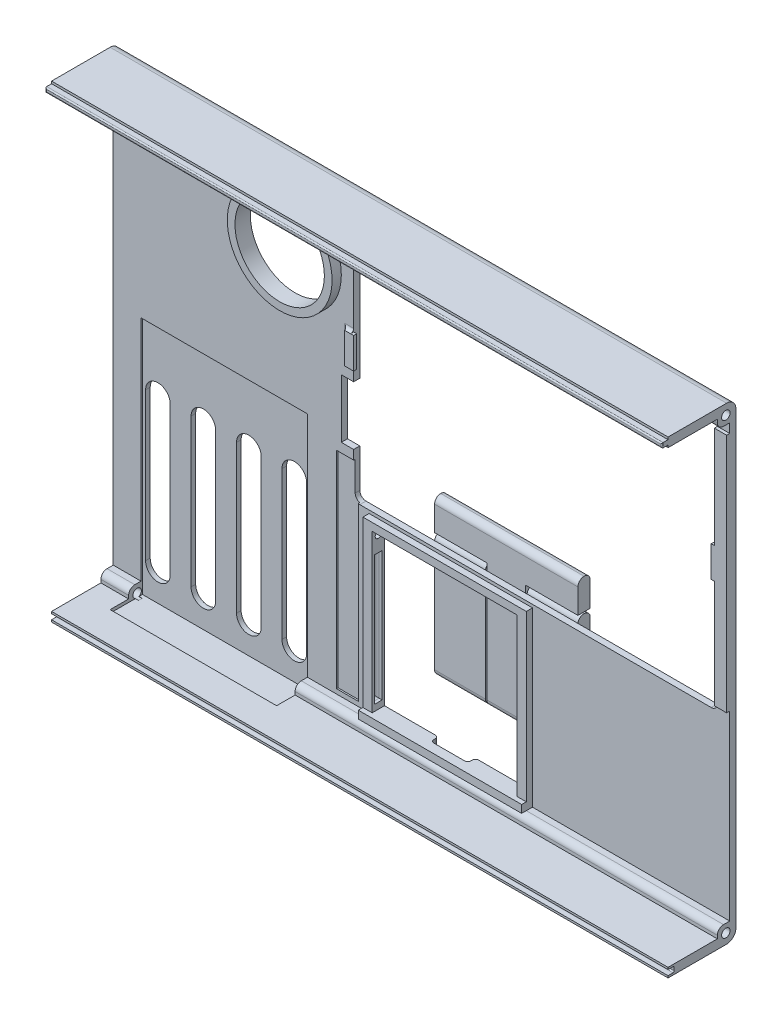
SolidWorks part; units mm, degrees
ref_plane "Front Plane" through (0, 0, 0) normal (0, 0, 1) x (1, 0, 0)
ref_plane "Top Plane" through (0, 0, 0) normal (0, 1, 0) x (1, 0, 0)
ref_plane "Right Plane" through (0, 0, 0) normal (1, 0, 0) x (0, 0, -1)
sketch "Sketch1" plane through (0, 0, 0) normal (0, 0, 1) x (1, 0, 0)
  line L1 (105, -90.3987) -> (-95, -90.3987)
  line L2 (105, -90.3987) -> (105, 61.6013)
  line L3 (105, 61.6013) -> (-95, 61.6013)
  line L4 (-95, -90.3987) -> (-95, 61.6013)
  line L5 (105, -90.3987) -> (-95, 61.6013) construction
  line L6 (105, 61.6013) -> (-95, -90.3987) construction
  point P0 (5, -14.3987)
  dimension "D1" = 200
  dimension "D2" = 152
extrude "body" add sketch "Sketch1" along normal blind 2
sketch "Sketch3" plane through (0, 0, 0) normal (0, 0, -1) x (-1, 0, 0)
  line L0 (95, -54.3987) -> (-105, -54.3987) construction
  line L1 (95, 61.6013) -> (95, -90.3987) construction
  line L2 (-105, -90.3987) -> (-105, 61.6013) construction
  line L3 (66.25, -78.3987) -> (66.25, -30.3987) construction
  line L4 (62.25, -78.3987) -> (62.25, -30.3987)
  line L5 (70.25, -78.3987) -> (70.25, -30.3987)
  line L6 (95, -30.3987) -> (-105, -30.3987) construction
  line L7 (81, -78.3987) -> (81, -30.3987) construction
  line L8 (95, -78.3987) -> (-105, -78.3987) construction
  line L9 (77, -78.3987) -> (77, -30.3987)
  line L10 (85, -78.3987) -> (85, -30.3987)
  line L11 (51.5, -78.3987) -> (51.5, -30.3987) construction
  line L12 (47.5, -78.3987) -> (47.5, -30.3987)
  line L13 (55.5, -78.3987) -> (55.5, -30.3987)
  line L14 (36.75, -78.3987) -> (36.75, -30.3987) construction
  line L15 (32.75, -78.3987) -> (32.75, -30.3987)
  line L16 (40.75, -78.3987) -> (40.75, -30.3987)
  line L17 (95, -90.3987) -> (95, 61.6013) construction
  line L18 (-105, 61.6013) -> (95, 61.6013) construction
  line L19 (95, -90.3987) -> (-105, -90.3987) construction
  line L20 (-105, -90.3987) -> (-105, 61.6013) construction
  circle A0 centre (38, 34.1013) radius 14.5
  arc A1 (62.25, -78.3987) -> (70.25, -78.3987) centre (66.25, -78.3987) ccw
  arc A2 (70.25, -30.3987) -> (62.25, -30.3987) centre (66.25, -30.3987) ccw
  arc A3 (77, -78.3987) -> (85, -78.3987) centre (81, -78.3987) ccw
  arc A4 (85, -30.3987) -> (77, -30.3987) centre (81, -30.3987) ccw
  arc A5 (47.5, -78.3987) -> (55.5, -78.3987) centre (51.5, -78.3987) ccw
  arc A6 (55.5, -30.3987) -> (47.5, -30.3987) centre (51.5, -30.3987) ccw
  arc A7 (32.75, -78.3987) -> (40.75, -78.3987) centre (36.75, -78.3987) ccw
  arc A8 (40.75, -30.3987) -> (32.75, -30.3987) centre (36.75, -30.3987) ccw
  point P10 (66.25, -54.3987)
  point P21 (81, -54.3987)
  point P27 (51.5, -54.3987)
  point P34 (36.75, -54.3987)
  dimension "D1" = 29
  dimension "D2" = 27.5
  dimension "D3" = 57
  dimension "D4" = 10
  dimension "D5" = 12
  dimension "D6" = 24
  dimension "D7" = 6.75
  dimension "D8" = 8
  dimension "D9" = 8
  dimension "D10" = 8
  dimension "D11" = 8
  dimension "D12" = 6.75
  dimension "D13" = 52.25
  dimension "D14" = 6.75
extrude "fan_exhaust_grill" cut sketch "Sketch3" against normal through all
sketch "Sketch12" plane through (0, 0, 2) normal (0, 0, 1) x (1, 0, 0)
  line L0 (-95, -90.3987) -> (-95, 61.6013) construction
  line L1 (105, -90.3987) -> (-95, -90.3987)
  line L2 (105, -90.3987) -> (105, -84.3987)
  line L3 (105, -84.3987) -> (-95, -84.3987)
  line L4 (-95, -90.3987) -> (-95, -84.3987)
  line L6 (105, 61.6013) -> (-95, 61.6013)
  line L7 (105, 61.6013) -> (105, 55.6013)
  line L8 (105, 55.6013) -> (-95, 55.6013)
  line L9 (-95, 61.6013) -> (-95, 55.6013)
  dimension "D1" = 6
  dimension "D2" = 6
extrude "side_walls" add sketch "Sketch12" along normal blind 20
sketch "Sketch14" plane through (105, 0, 0) normal (1, 0, 0) x (0, 0, -1)
  line L0 (-22, -90.3987) -> (0, -90.3987) construction
  line L1 (0, -90.3987) -> (0, 61.6013) construction
  line L2 (-22, 61.6013) -> (0, 61.6013) construction
  circle A0 centre (-3.25, -87.1487) radius 1.375
  circle A1 centre (-3.25, 58.3513) radius 1.375
  dimension "D1" = 2.75
  dimension "D2" = 2.75
  dimension "D3" = 3.25
  dimension "D4" = 3.25
  dimension "D5" = 3.25
  dimension "D6" = 3.25
  dimension "D7" = 145.5
extrude "mount_holes_l" cut sketch "Sketch14" against normal blind 10 and the other way through all
sketch "Sketch16" plane through (-95, 0, 0) normal (-1, 0, 0) x (0, 0, 1)
  line L0 (0, -90.3987) -> (0, 61.6013) construction
  line L2 (22, 61.6013) -> (0, 61.6013) construction
  line L3 (22, -90.3987) -> (0, -90.3987) construction
  circle A0 centre (3.25, -87.1487) radius 1.375
  circle A1 centre (3.25, 58.3513) radius 1.375
  dimension "D1" = 2.75
  dimension "D4" = 2.75
  dimension "D2" = 3.25
  dimension "D3" = 3.25
  dimension "D5" = 3.25
  dimension "D6" = 3.25
extrude "mount_holes_r" cut sketch "Sketch16" against normal blind 10
sketch "Sketch18" plane through (105, 0, 0) normal (1, 0, 0) x (0, 0, -1)
  line L1 (-22, -84.3987) -> (-6, -84.3987)
  line L2 (-22, -84.3987) -> (-22, -87.3987)
  line L3 (-22, -87.3987) -> (-6, -87.3987)
  line L4 (-6, -84.3987) -> (-6, -87.3987)
  line L5 (-22, 55.6013) -> (-6, 55.6013)
  line L6 (-22, 55.6013) -> (-22, 58.6013)
  line L7 (-22, 58.6013) -> (-6, 58.6013)
  line L8 (-6, 55.6013) -> (-6, 58.6013)
  dimension "D1" = 3
  dimension "D2" = 16
  dimension "D3" = 3
  dimension "D4" = 16
extrude "wall_reduce" cut sketch "Sketch18" against normal through all
sketch "Sketch19" plane through (0, 0, 22) normal (0, 0, 1) x (1, 0, 0)
  line L0 (-95, -90.3987) -> (-95, 61.6013) construction
  line L1 (-95, -89.7487) -> (105, -89.7487)
  line L2 (-95, -89.7487) -> (-95, -88.0487)
  line L3 (-95, -88.0487) -> (105, -88.0487)
  line L4 (105, -89.7487) -> (105, -88.0487)
  line L5 (105, -90.3987) -> (105, 61.6013) construction
  line L6 (-95, -90.3987) -> (105, -90.3987) construction
  line L7 (-95, -87.3987) -> (105, -87.3987) construction
  dimension "D1" = 0.65
  dimension "D2" = 1.7
  dimension "D3" = 0.65
extrude "groove" cut sketch "Sketch19" against normal blind 2
sketch "Sketch20" plane through (0, 0, 22) normal (0, 0, 1) x (1, 0, 0)
  line L0 (-95, -90.3987) -> (-95, 61.6013) construction
  line L1 (-95, 59.3513) -> (105, 59.3513)
  line L2 (-95, 59.3513) -> (-95, 60.8513)
  line L3 (-95, 60.8513) -> (105, 60.8513)
  line L4 (105, 59.3513) -> (105, 60.8513)
  line L5 (105, -90.3987) -> (105, 61.6013) construction
  line L6 (105, 61.6013) -> (-95, 61.6013) construction
  dimension "D1" = 0.75
  dimension "D2" = 1.5
extrude "notch" add sketch "Sketch20" along normal blind 2
sketch "Sketch21" plane through (0, 0, 2) normal (0, 0, 1) x (1, 0, 0)
  line L0 (105, -90.3987) -> (105, 61.6013) construction
  line L1 (101, -27.3987) -> (-17, -27.3987)
  line L2 (101, -27.3987) -> (101, 55.1013)
  line L3 (101, 55.1013) -> (-17, 55.1013)
  line L4 (-17, -27.3987) -> (-17, 55.1013)
  line L5 (105, 61.6013) -> (-95, 61.6013) construction
  dimension "D1" = 118
  dimension "D2" = 82.5
  dimension "D3" = 4
  dimension "D4" = 6.5
extrude "batt_cut" cut sketch "Sketch21" against normal through all
fillet "Fillet1" radius 3 2 edges at (5, -90.3987, 0) (5, 61.6013, 0)
fillet "Fillet2" radius 2 2 edges at (5, -84.3987, 6) (5, 55.6013, 6)
fillet "Fillet3" radius 0.4 6 edges at (5, 60.8513, 24) (105, 60.1013, 24) (5, 59.3513, 24) (-95, 60.1013, 24) (5, -89.7487, 20) (5, -88.0487, 20)
fillet "Fillet4" radius 2 4 edges at (-17, -27.3987, 1) (101, -27.3987, 1) (101, 55.1013, 1) (-17, 55.1013, 1)
sketch "Sketch22" plane through (0, 0, 2) normal (0, 0, 1) x (1, 0, 0)
  circle A0 centre (-38, 34.1013) radius 14.5
  circle A1 centre (-38, 34.1013) radius 17
  dimension "D1" = 29
  dimension "D2" = 34
extrude "fan_hole_supp" add sketch "Sketch22" along normal blind 3
sketch "Sketch23" plane through (0, 0, 2) normal (0, 0, 1) x (1, 0, 0)
  line L0 (105, -90.3987) -> (105, 61.6013) construction
  line L1 (105, 52.6013) -> (101, 52.6013)
  line L2 (105, 52.6013) -> (105, -25.3987)
  line L3 (105, -25.3987) -> (101, -25.3987)
  line L4 (101, 52.6013) -> (101, -25.3987)
  arc A0 (99, -27.3987) -> (101, -25.3987) centre (99, -25.3987) ccw construction
  dimension "D1" = 78
  dimension "D2" = 4
extrude "batt_cut_supp" add sketch "Sketch23" along normal blind 1
sketch "Sketch24" plane through (0, 0, 2) normal (0, 0, 1) x (1, 0, 0)
  line L0 (-95, -90.3987) -> (-95, 61.6013) construction
  line L1 (-86, -10.3987) -> (-32, -10.3987)
  line L2 (-86, -10.3987) -> (-86, -88.3987)
  line L3 (-86, -88.3987) -> (-32, -88.3987)
  line L4 (-32, -10.3987) -> (-32, -88.3987)
  line L5 (-95, -90.3987) -> (105, -90.3987) construction
  line L7 (-22.5, -15.8987) -> (-15.5, -15.8987)
  line L8 (-22.5, -15.8987) -> (-22.5, -82.8987)
  line L9 (-22.5, -82.8987) -> (-15.5, -82.8987)
  line L10 (-15.5, -15.8987) -> (-15.5, -82.8987)
  dimension "D1" = 9
  dimension "D2" = 2
  dimension "D3" = 54
  dimension "D4" = 78
  dimension "D5" = 9.5
  dimension "D6" = 7
  dimension "D7" = 67
  dimension "D8" = 5.5
  dimension "D9" = 5.5
extrude "Cut-Extrude1" cut sketch "Sketch24" against normal blind 10.5 from offset 10
sketch "Sketch25" plane through (0, 0, 2) normal (0, 0, 1) x (1, 0, 0)
  line L7 (-17, 53.1013) -> (-17, -15.8987) construction
  line L8 (-17, 6.1013) -> (-21, 6.1013)
  line L9 (-17, 6.1013) -> (-17, -12.8987)
  line L10 (-17, -12.8987) -> (-21, -12.8987)
  line L11 (-21, 6.1013) -> (-21, -12.8987)
  line L12 (-15, -27.3987) -> (99, -27.3987) construction
  dimension "D1" = 14.5
  dimension "D2" = 19
  dimension "D3" = 4
extrude "Cut-Extrude2" cut sketch "Sketch25" against normal through all
sketch "Sketch26" plane through (0, 0, 2) normal (0, 0, 1) x (1, 0, 0)
  line L0 (-17, 53.1013) -> (-17, 6.1013) construction
  line L1 (-17, 20.1013) -> (-19, 20.1013)
  line L2 (-17, 20.1013) -> (-17, 10.1013)
  line L3 (-17, 10.1013) -> (-19, 10.1013)
  line L4 (-19, 20.1013) -> (-19, 10.1013)
  line L10 (99, 55.1013) -> (-15, 55.1013) construction
  dimension "D4" = 2
  dimension "D5" = 10
  dimension "D6" = 35
extrude "Boss-Extrude1" add sketch "Sketch26" along normal blind 1
sketch "Sketch27" plane through (-17, 0, 0) normal (1, 0, 0) x (0, 0, -1)
  line L0 (-3, 10.1013) -> (-3, 20.1013) construction
  line L1 (-3, 20.1013) -> (-2, 20.1013)
  line L2 (-3, 20.1013) -> (-3, 10.1013)
  line L3 (-3, 10.1013) -> (-2, 10.1013)
  line L4 (-2, 20.1013) -> (-2, 10.1013)
  line L5 (-3, 20.1013) -> (-2, 20.1013) construction
extrude "Boss-Extrude2" add sketch "Sketch27" along normal blind 1
sketch "Sketch28" plane through (101, 0, 0) normal (-1, 0, 0) x (0, 0, 1)
  line L0 (0, -25.3987) -> (0, 53.1013) construction
  line L1 (2, 9.6013) -> (3, 9.6013)
  line L2 (2, 9.6013) -> (2, 19.6013)
  line L3 (2, 19.6013) -> (3, 19.6013)
  line L4 (3, 9.6013) -> (3, 19.6013)
  line L5 (3, 52.6013) -> (2, 52.6013) construction
  dimension "D1" = 1
  dimension "D2" = 2
  dimension "D3" = 10
  dimension "D4" = 33
extrude "Boss-Extrude3" add sketch "Sketch28" along normal blind 1
fillet "Fillet5" radius 1 3 edges at (-18, 20.1013, 2) (-18, 10.1013, 2) (-19, 15.1013, 2)
sketch "Sketch29" plane through (0, 0, 2) normal (0, 0, 1) x (1, 0, 0)
  line L1 (-9, -30.8987) -> (38, -30.8987)
  line L2 (-9, -30.8987) -> (-9, -81.8987)
  line L3 (-9, -81.8987) -> (38, -81.8987)
  line L4 (38, -30.8987) -> (38, -81.8987)
  line L5 (105, -90.3987) -> (105, 61.6013) construction
  line L7 (-95, -90.3987) -> (105, -90.3987) construction
  dimension "D1" = 67
  dimension "D2" = 47
  dimension "D3" = 51
  dimension "D4" = 8.5
extrude "stand_cut" cut sketch "Sketch29" against normal through all
sketch "Sketch30" plane through (0, 0, 2) normal (0, 0, 1) x (1, 0, 0)
  line L0 (-9, -81.8987) -> (38, -30.8987) construction
  line L1 (38, -30.8987) -> (-9, -30.8987) construction
  line L2 (38, -81.8987) -> (38, -30.8987) construction
  line L3 (-9, -30.8987) -> (38, -81.8987) construction
  line L5 (41, -84.3987) -> (-12, -84.3987)
  line L6 (41, -84.3987) -> (41, -28.3987)
  line L7 (41, -28.3987) -> (-12, -28.3987)
  line L8 (-12, -84.3987) -> (-12, -28.3987)
  line L9 (41, -84.3987) -> (-12, -28.3987) construction
  line L10 (41, -28.3987) -> (-12, -84.3987) construction
  line L11 (38, -81.8987) -> (-9, -81.8987)
  line L12 (38, -81.8987) -> (38, -30.8987)
  line L13 (38, -30.8987) -> (-9, -30.8987)
  line L14 (-9, -81.8987) -> (-9, -30.8987)
  line L15 (38, -81.8987) -> (-9, -30.8987) construction
  line L16 (38, -30.8987) -> (-9, -81.8987) construction
  point P11 (14.5, -56.3987)
  point P16 (14.5, -56.3987)
  dimension "D1" = 3
  dimension "D2" = 2.5
extrude "stand_extra_support" add sketch "Sketch30" along normal blind 2
sketch "Sketch31" plane through (-9, 0, 0) normal (1, 0, 0) x (0, 0, -1)
  line L0 (-2, -23.8792) -> (-2, -81.8987) construction
  line L1 (0, -81.8987) -> (-4, -81.8987) construction
  line L2 (0, -30.8987) -> (0, -81.8987) construction
  line L3 (-0.75, -79.8987) -> (-3.25, -79.8987)
  line L4 (-0.75, -79.8987) -> (-0.75, -37.8987)
  line L5 (-0.75, -37.8987) -> (-3.25, -37.8987)
  line L6 (-3.25, -79.8987) -> (-3.25, -37.8987)
  line L7 (-0.75, -79.8987) -> (-3.25, -37.8987) construction
  line L8 (-0.75, -37.8987) -> (-3.25, -79.8987) construction
  line L9 (0, -30.8987) -> (-4, -30.8987) construction
  circle A0 centre (-2, -32.8987) radius 1
  point P4 (-2, -58.8987)
  dimension "D6" = 2
  dimension "D1" = 2
  dimension "D2" = 42
  dimension "D3" = 2.5
  dimension "D4" = 0.75
  dimension "D5" = 2
extrude "stand_right_groove" cut sketch "Sketch31" against normal blind 2
sketch "Sketch32" plane through (38, 0, 0) normal (-1, 0, 0) x (0, 0, 1)
  line L0 (2, -81.8987) -> (2, -30.8421) construction
  line L1 (0, -81.8987) -> (4, -81.8987) construction
  line L2 (0, -30.8987) -> (4, -30.8987) construction
  line L3 (3.25, -37.8987) -> (0.75, -37.8987)
  line L4 (3.25, -37.8987) -> (3.25, -79.8987)
  line L5 (3.25, -79.8987) -> (0.75, -79.8987)
  line L6 (0.75, -37.8987) -> (0.75, -79.8987)
  line L7 (3.25, -37.8987) -> (0.75, -79.8987) construction
  line L8 (3.25, -79.8987) -> (0.75, -37.8987) construction
  circle A0 centre (2, -32.8987) radius 1
  point P4 (2, -58.8987)
  dimension "D5" = 2
  dimension "D1" = 2.5
  dimension "D2" = 42
  dimension "D3" = 2
  dimension "D4" = 2
extrude "stand_left_groove" cut sketch "Sketch32" against normal blind 2
fillet "Fillet6" radius 1 8 edges at (40, -37.8987, 2) (40, -58.8987, 3.25) (40, -79.8987, 2) (40, -58.8987, 0.75) (-11, -37.8987, 2) (-11, -58.8987, 0.75) (-11, -79.8987, 2) (-11, -58.8987, 3.25)
sketch "Sketch33" plane through (0, 0, 0) normal (0, 0, -1) x (-1, 0, 0)
  line L0 (-14.5, -81.8987) -> (-14.5, -30.8987) construction
  line L1 (9, -81.8987) -> (-38, -81.8987) construction
  line L2 (-38, -30.8987) -> (9, -30.8987) construction
  line L3 (-105, -87.3987) -> (95, -87.3987) construction
  line L4 (-8.5, -84.8987) -> (-20.5, -84.8987)
  line L5 (-8.5, -84.8987) -> (-8.5, -81.8987)
  line L6 (-8.5, -81.8987) -> (-20.5, -81.8987)
  line L7 (-20.5, -84.8987) -> (-20.5, -81.8987)
  line L8 (-8.5, -84.8987) -> (-20.5, -81.8987) construction
  line L9 (-8.5, -81.8987) -> (-20.5, -84.8987) construction
  point P6 (-14.5, -83.3987)
  dimension "D1" = 2.5
  dimension "D2" = 3
  dimension "D3" = 12
extrude "finger_notch" cut sketch "Sketch33" against normal blind 2.5
fillet "Fillet7" radius 1 6 edges at (8.5, -83.3987, 2.5) (8.5, -83.3987, 0) (20.5, -83.3987, 0) (14.5, -84.8987, 0) (20.5, -83.3987, 2.5) (14.5, -84.8987, 2.5)
sketch "Sketch34" plane through (0, 0, 4) normal (0, 0, 1) x (1, 0, 0)
  line L0 (41, -84.3987) -> (41, -28.3987) construction
  line L1 (-12, -84.3987) -> (41, -84.3987)
  line L2 (-12, -84.3987) -> (-12, -81.8987)
  line L3 (-12, -81.8987) -> (41, -81.8987)
  line L4 (41, -84.3987) -> (41, -81.8987)
  dimension "D1" = 2.5
extrude "back_lid_ext" add sketch "Sketch34" along normal blind 1.5
sketch "Sketch35" [suppressed] plane through (0, -81.8987, 0) normal (0, 1, 0) x (1, 0, 0)
  line L1 (-12, -5.5) -> (41, -5.5)
  line L2 (-12, -5.5) -> (-12, -4)
  line L3 (-12, -4) -> (41, -4)
  line L4 (41, -5.5) -> (41, -4)
extrude "stand_lid" [suppressed] add sketch "Sketch35" along normal blind 2
sketch "Sketch36" plane through (0, 0, 0) normal (0, 0, -1) x (-1, 0, 0)
  line L0 (-38, -30.8987) -> (9, -30.8987) construction
  line L1 (-37.75, -31.1487) -> (8.75, -31.1487)
  line L2 (-37.75, -31.1487) -> (-37.75, -81.6487)
  line L3 (-37.75, -81.6487) -> (8.75, -81.6487)
  line L4 (8.75, -31.1487) -> (8.75, -81.6487)
  line L5 (-38, -81.8987) -> (-38, -30.8987) construction
  dimension "D1" = 50.5
  dimension "D2" = 0.25
  dimension "D3" = 0.25
  dimension "D4" = 46.5
extrude "st_body" add sketch "Sketch36" against normal blind 4 from offset 20 separate body
sketch "Sketch37" plane through (0, 0, -20) normal (0, 0, -1) x (-1, 0, 0)
  line L0 (-37.75, -41.1487) -> (-20.75, -41.1487)
  line L1 (-37.75, -31.1487) -> (-37.75, -81.6487) construction
  line L2 (-20.75, -41.1487) -> (-20.75, -81.6487)
  line L3 (-37.75, -81.6487) -> (8.75, -81.6487) construction
  line L4 (-37.75, -41.6487) -> (-21.25, -41.6487)
  line L5 (-21.25, -41.6487) -> (-21.25, -81.6487)
  line L6 (8.75, -41.1487) -> (-8.25, -41.1487)
  line L7 (8.75, -81.6487) -> (8.75, -31.1487) construction
  line L8 (-8.25, -41.1487) -> (-8.25, -81.6487)
  line L9 (8.75, -41.6487) -> (-7.75, -41.6487)
  line L10 (-7.75, -41.6487) -> (-7.75, -81.6487)
  line L11 (-37.75, -41.1487) -> (-37.75, -41.6487)
  line L12 (8.75, -41.1487) -> (8.75, -41.6487)
  line L13 (-21.25, -81.6487) -> (-20.75, -81.6487)
  line L14 (-8.25, -81.6487) -> (-7.75, -81.6487)
  line L15 (8.75, -31.1487) -> (-37.75, -31.1487) construction
  dimension "D1" = 0.5
  dimension "D2" = 0.5
  dimension "D3" = 0.5
  dimension "D4" = 0.5
  dimension "D5" = 10
  dimension "D6" = 10
  dimension "D7" = 16.5
  dimension "D8" = 16.5
extrude "st_body_cut" cut sketch "Sketch37" against normal blind 4
fillet "Fillet8" radius 2 4 edges at (29.5, -41.6487, -16) (29.5, -41.6487, -20) (29.5, -81.6487, -16) (29.5, -81.6487, -20)
fillet "Fillet9" radius 2 4 edges at (-0.5, -41.6487, -16) (-0.5, -81.6487, -16) (-0.5, -81.6487, -20) (-0.5, -41.6487, -20)
fillet "Fillet10" radius 2 4 edges at (14.5, -31.1487, -20) (14.5, -81.6487, -20) (14.5, -81.6487, -16) (14.5, -31.1487, -16)
sketch "Sketch39" plane through (-8.75, 0, 0) normal (-1, 0, 0) x (0, 0, 1)
  line L0 (-18, -41.6487) -> (-18, -81.6487) construction
  circle A0 centre (-18, -79.6487) radius 1.25
  dimension "D2" = 2.5
  dimension "D1" = 2
extrude "st_hinge_hole_l" cut sketch "Sketch39" against normal blind 10 from offset 6.5 offset against normal yes
sketch "Sketch40" plane through (37.75, 0, 0) normal (1, 0, 0) x (0, 0, -1)
  line L0 (18, -41.6487) -> (18, -81.6487) construction
  circle A0 centre (18, -79.6487) radius 1.25
  dimension "D2" = 2.5
  dimension "D1" = 2
extrude "st_hinge_hole_r" cut sketch "Sketch40" against normal blind 10 from offset 6.5 offset against normal yes
sketch "Sketch41" plane through (20.75, 0, 0) normal (1, 0, 0) x (0, 0, -1)
  line L0 (18, -41.1487) -> (18, -81.6487) construction
  line L1 (16, -41.1487) -> (20, -41.1487) construction
  circle A0 centre (18, -79.6487) radius 0.9
  dimension "D2" = 1.8
  dimension "D1" = 2
extrude "st_hinge_rod" add sketch "Sketch41" against normal blind 26.5 from offset 7
sketch "Sketch42" plane through (0, 0, -20) normal (0, 0, -1) x (-1, 0, 0)
  line L0 (-21.25, -43.6487) -> (-7.75, -43.6487) construction
  line L1 (-21.25, -43.6487) -> (-37.75, -43.6487) construction
  line L2 (-21.25, -43.6487) -> (-21.25, -79.6487) construction
  line L3 (-20.75, -79.6487) -> (-20.75, -41.1487) construction
  line L4 (-20.75, -43.6487) -> (-8.25, -43.6487)
  line L5 (-20.75, -43.6487) -> (-20.75, -49.6487)
  line L6 (-20.75, -49.6487) -> (-8.25, -49.6487)
  line L7 (-8.25, -43.6487) -> (-8.25, -49.6487)
  line L8 (-8.25, -41.1487) -> (-8.25, -79.6487) construction
  dimension "D1" = 6
extrude "st_conn_cut" cut sketch "Sketch42" against normal blind 2
sketch "Sketch43" plane through (21.25, 0, 0) normal (-1, 0, 0) x (0, 0, 1)
  line L0 (-20, -43.6487) -> (-20, -79.6487) construction
  line L1 (-20, -45.1487) -> (-18.5, -45.1487)
  line L2 (-20, -45.1487) -> (-20, -49.1487)
  line L3 (-20, -49.1487) -> (-18.5, -49.1487)
  line L4 (-18.5, -45.1487) -> (-18.5, -49.1487)
  dimension "D1" = 3.5
  dimension "D2" = 1.5
  dimension "D3" = 4
extrude "st_conn_piece" add sketch "Sketch43" along normal blind 13.5
